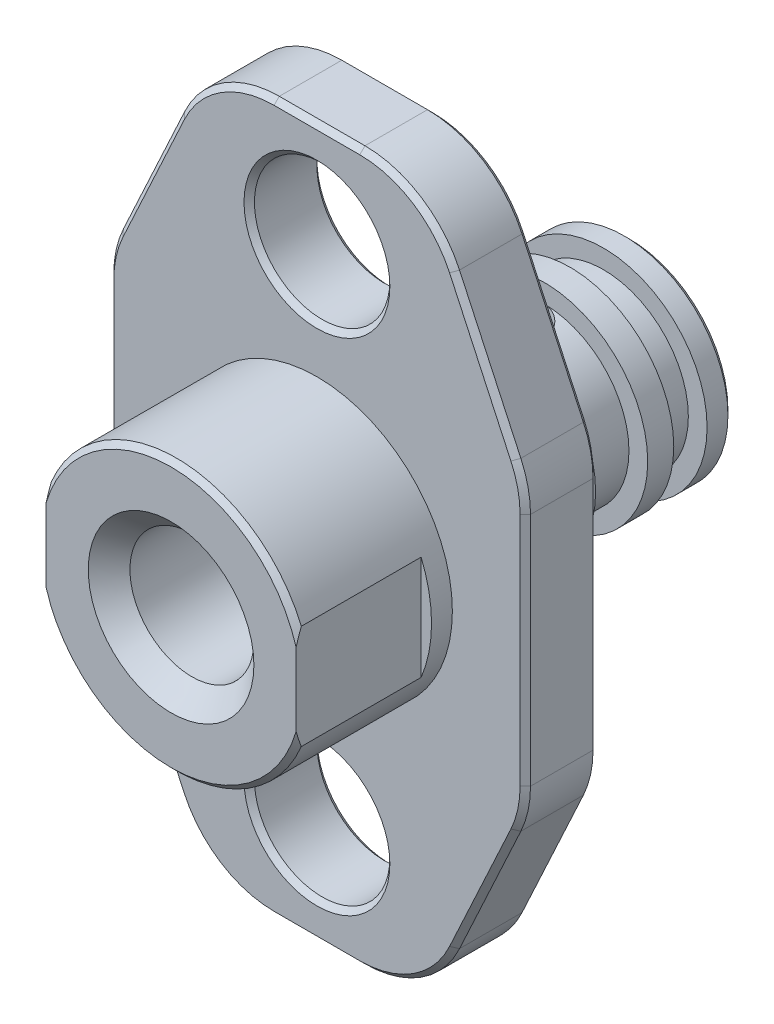
SolidWorks part; units mm, degrees
material "316 S/Steel"
ref_plane "Front" through (0, 0, 0) normal (0, 0, 1) x (1, 0, 0)
ref_plane "Top" through (0, 0, 0) normal (0, 1, 0) x (1, 0, 0)
ref_plane "Right" through (0, 0, 0) normal (1, 0, 0) x (0, 0, -1)
sketch "Sketch1" plane through (0, 0, 0) normal (1, 0, 0) x (0, 0, -1)
  line L0 (0, 0) -> (44, 0) construction
  line L1 (14, 13) -> (0.5, 13)
  line L2 (0.5, 13) -> (0, 12.5)
  line L3 (14, 13) -> (14, 35)
  line L4 (14, 35) -> (21, 35)
  line L5 (21, 35) -> (21, 9.95)
  line L6 (21, 9.95) -> (25.1, 9.95)
  line L7 (25.1, 9.95) -> (25.1, 8.15)
  line L8 (25.1, 8.15) -> (28.3, 8.15)
  line L9 (28.3, 8.15) -> (28.3, 9.95)
  line L10 (28.3, 9.95) -> (30.8, 9.95)
  line L11 (30.8, 9.95) -> (30.8, 8.15)
  line L12 (30.8, 8.15) -> (35.8, 8.15)
  line L13 (35.8, 8.15) -> (35.8, 9.95)
  line L14 (35.8, 9.95) -> (38.3, 9.95)
  line L15 (38.3, 9.95) -> (38.3, 8.15)
  line L16 (38.3, 8.15) -> (41.5, 8.15)
  line L17 (41.5, 8.15) -> (41.5, 9.95)
  line L18 (41.5, 9.95) -> (43.5, 9.95)
  line L19 (43.5, 9.95) -> (44, 9.45)
  line L20 (44, 9.45) -> (44, 0)
  line L21 (0, 12.5) -> (0, 7.95)
  line L22 (2, 5.95) -> (19, 5.95)
  line L23 (20.1717, 4) -> (38, 4)
  line L24 (19, 5.95) -> (20.1717, 4)
  line L25 (38, 4) -> (40.4034, 0)
  line L26 (40.4034, 0) -> (44, 0)
  line L27 (0, 4) -> (44, 4) construction
  line L28 (0, 5.95) -> (44, 5.95) construction
  line L29 (0, 7.95) -> (2, 5.95)
  dimension "D1" = 44
  dimension "D2" = 13
  dimension "D3" = 9.95
  dimension "D4" = 8.15
  dimension "D5" = 14
  dimension "D6" = 7
  dimension "D7" = 35
  dimension "D8" = 4.1
  dimension "D9" = 3.2
  dimension "D10" = 2.5
  dimension "D11" = 5
  dimension "D12" = 2.5
  dimension "D13" = 3.2
  dimension "D14" = 2.5
  dimension "D15" = 45
  dimension "D16" = 0.5
  dimension "D17" = 45
  dimension "D18" = 0.5
  dimension "D19" = 19
  dimension "D20" = 5.95
  dimension "D21" = 4
  dimension "D22" = 59
  dimension "D23" = 38
  dimension "D24" = 59
  dimension "D25" = 2
  dimension "D26" = 45
revolve "Revolve1" add sketch "Sketch1" angle 360 about L0
cosmetic thread "Cosmetic Thread1" parameters "D2"=14.2875
sketch "Sketch3" plane through (0, 0, 0) normal (0, 0, 1) x (1, 0, 0)
  line L0 (0, 34) -> (0, -34) construction
  line L1 (-20, 0) -> (20, 0) construction
  line L2 (-20, 11.2955) -> (-20, -11.2955)
  line L3 (13.1857, 28.2046) -> (19.0731, 15.5001)
  line L4 (20, 11.2955) -> (20, -11.2955)
  line L5 (-4.1126, 34) -> (4.1126, 34)
  line L6 (-13.1857, 28.2046) -> (-19.0731, 15.5001)
  line L7 (13.1857, -28.2046) -> (19.0731, -15.5001)
  line L8 (-20, 34) -> (-20, -34) construction
  line L9 (-20, 34) -> (20, 34) construction
  line L10 (-4.1126, -34) -> (4.1126, -34)
  line L11 (-13.1857, -28.2046) -> (-19.0731, -15.5001)
  arc A0 (-13.1857, 28.2046) -> (-4.1126, 34) centre (-4.1126, 24) cw
  arc A1 (-19.0731, 15.5001) -> (-20, 11.2955) centre (-10, 11.2955) ccw
  arc A2 (13.1857, 28.2046) -> (4.1126, 34) centre (4.1126, 24) ccw
  arc A3 (19.0731, 15.5001) -> (20, 11.2955) centre (10, 11.2955) cw
  arc A4 (19.0731, -15.5001) -> (20, -11.2955) centre (10, -11.2955) ccw
  arc A5 (13.1857, -28.2046) -> (4.1126, -34) centre (4.1126, -24) cw
  arc A6 (-13.1857, -28.2046) -> (-4.1126, -34) centre (-4.1126, -24) ccw
  arc A7 (-19.0731, -15.5001) -> (-20, -11.2955) centre (-10, -11.2955) cw
  circle A8 centre (0, 24) radius 6.5
  circle A9 centre (0, -24) radius 6.5
  point P7 (0, 0)
  point P11 (0, 0)
  point P14 (20, -34)
  point P19 (-10.5, 34)
  point P22 (-20, 13.5)
  dimension "D5" = 10
  dimension "D6" = 13
  dimension "D1" = 40
  dimension "D2" = 68
  dimension "D3" = 13.5
  dimension "D4" = 10.5
  dimension "D7" = 24
extrude "Cut-Extrude1" cut sketch "Sketch3" against normal blind 21 flip side to cut
sketch "Sketch4" plane through (0, 0, 0) normal (1, 0, 0) x (0, 0, -1)
  line L0 (33.3, 12.4096) -> (33.3, -12.4096)
  line L1 (35.8, 12.4096) -> (35.8, -12.4096)
  line L2 (33.3, 12.4096) -> (35.8, 12.4096)
  line L3 (33.3, -12.4096) -> (35.8, -12.4096)
  line L4 (44, -9.45) -> (44, 9.45) construction
  point P3 (33.3, 0)
  dimension "D1" = 10.7
  dimension "D2" = 2.5
revolve "Cut-Revolve1" cut sketch "Sketch4" angle 360 about L0
sketch "Sketch7" plane through (0, 0, 0) normal (0, 0, 1) x (1, 0, 0)
  line L0 (0, 0) -> (-12, 0) construction
  line L2 (-12, 6.6844) -> (-14.3589, 6.6844)
  line L3 (-14.3589, 6.6844) -> (-14.3589, -8.3156)
  line L4 (-14.3589, -8.3156) -> (-12, -8.3156)
  line L6 (-12, 6.6844) -> (-12, -8.3156)
  dimension "D1" = 12
  dimension "D2" = 15
extrude "Cut-Extrude2" cut sketch "Sketch7" against normal blind 12
pattern_circular "CirPattern1" count 2 over 180 about axis through (0, 0, 0) along (0, 0, 1) of "Cut-Extrude2" reverse direction yes
chamfer "Chamfer1" distance 0.5 angle 45 36 edges at (-6.5, 24, -14) (6.5, 24, -21) (-6.5, -24, -14) (-6.5, -24, -21) (-9.4956, 32.4275, -14) (0, 34, -14) (-16.1294, 21.8524, -14) (9.4956, 32.4275, -14) (-19.7655, 13.4483, -14) (16.1294, 21.8524, -14) (-20, 0, -14) (19.7655, 13.4483, -14) (-19.7655, -13.4483, -14) (20, 0, -14) (-16.1294, -21.8524, -14) (19.7655, -13.4483, -14) (-9.4956, -32.4275, -14) (16.1294, -21.8524, -14) (0, -34, -14) (9.4956, -32.4275, -14) (-16.1294, 21.8524, -21) (-19.7655, 13.4483, -21) (-9.4956, 32.4275, -21) (-20, 0, -21) (0, 34, -21) (-19.7655, -13.4483, -21) (9.4956, 32.4275, -21) (-16.1294, -21.8524, -21) (16.1294, 21.8524, -21) (-9.4956, -32.4275, -21) (19.7655, 13.4483, -21) (0, -34, -21) (20, 0, -21) (9.4956, -32.4275, -21) (19.7655, -13.4483, -21) (16.1294, -21.8524, -21)
